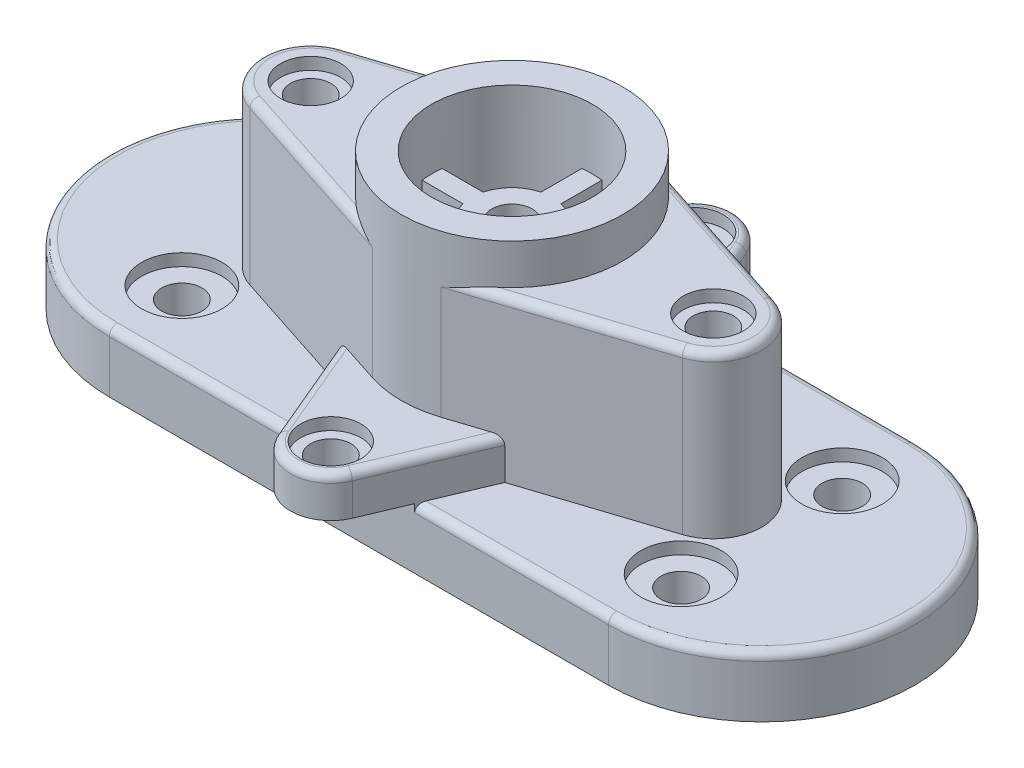
SolidWorks part; units mm, degrees
ref_plane "Front Plane" through (0, 0, 0) normal (0, 0, 1) x (1, 0, 0)
ref_plane "Top Plane" through (0, 0, 0) normal (0, 1, 0) x (1, 0, 0)
ref_plane "Right Plane" through (0, 0, 0) normal (1, 0, 0) x (0, 0, -1)
sketch "Sketch1" plane through (0, 0, 0) normal (0, 1, 0) x (1, 0, 0)
  line L0 (-62, 0) -> (62, 0) construction
  line L1 (-62, 38) -> (62, 38)
  line L2 (-62, -38) -> (62, -38)
  arc A0 (-62, 38) -> (-62, -38) centre (-62, 0) ccw
  arc A1 (62, -38) -> (62, 38) centre (62, 0) ccw
  point P2 (0, 0)
  dimension "D1" = 76
  dimension "D2" = 124
extrude "Boss-Extrude1" add sketch "Sketch1" along normal mid plane 15
sketch "Sketch2" plane through (0, 7.5, 0) normal (0, 1, 0) x (1, 0, 0)
  circle A0 centre (0, 0) radius 27.5
  dimension "D1" = 55
extrude "Boss-Extrude2" add sketch "Sketch2" along normal blind 50
hole_wizard "Hole1" positions "Sketch3" profile "Sketch4" legacy end condition through all
sketch "Sketch3" plane through (0, 7.5, 0) normal (0, 1, 0) x (1, 0, 0)
  point P0 (62, 20)
  dimension "D1" = 62
  dimension "D2" = 20
sketch "Sketch4" plane through (62, 7.5, -20) normal (1, 0, 0) x (0, 0, 1)
  line L0 (0, 0) -> (0, 18.0043)
  line L1 (0, 18.0043) -> (5, 15)
  line L2 (5, 15) -> (5, 3)
  line L3 (5, 3) -> (10, 3)
  line L4 (10, 0) -> (0, 0)
  line L5 (0, -11.3109) -> (0, 121.1557) construction
  line L6 (0, 18.0043) -> (-5, 15) construction
  line L7 (10, 3) -> (10, 0)
  dimension "Depth" = 15
  dimension "Drill Angle" = 118
  dimension "Diameter" = 10
  dimension "C-Bore Diameter" = 20
  dimension "C-Bore Depth" = 3
mirror "Mirror1" about plane through (0, 0, 0) normal (0, 0, 1) of "Hole1"
mirror "Mirror2" about plane through (0, 0, 0) normal (1, 0, 0) of "Hole1", "Mirror1"
hole_wizard "Hole2" positions "Sketch5" profile "Sketch6" legacy end condition through all
sketch "Sketch5" plane through (0, 57.5, 0) normal (0, 1, 0) x (1, 0, 0)
  point P0 (0, 0)
sketch "Sketch6" plane through (0, 57.5, 0) normal (1, 0, 0) x (0, 0, 1)
  line L0 (0, 0) -> (0, 68.0043)
  line L1 (0, 68.0043) -> (5, 65)
  line L2 (5, 65) -> (5, 15)
  line L3 (5, 15) -> (20, 15)
  line L4 (20, 0) -> (0, 0)
  line L5 (0, -11.3109) -> (0, 121.1557) construction
  line L6 (0, 68.0043) -> (-5, 65) construction
  line L7 (20, 15) -> (20, 0)
  dimension "Depth" = 65
  dimension "Drill Angle" = 118
  dimension "Diameter" = 10
  dimension "C-Bore Diameter" = 40
  dimension "C-Bore Depth" = 15
sketch "Sketch7" plane through (0, 7.5, 0) normal (0, 1, 0) x (1, 0, 0)
  line L0 (-53.72, 11.4088) -> (-8.525, 26.1453)
  line L1 (0, 0) -> (37.4038, 0) construction
  line L2 (0, 0) -> (0, 58.2008) construction
  line L3 (-53.72, -11.4088) -> (-8.525, -26.1453)
  line L4 (53.72, 11.4088) -> (8.525, 26.1453)
  line L5 (53.72, -11.4088) -> (8.525, -26.1453)
  circle A0 centre (0, 0) radius 27.5 construction
  arc A1 (-8.525, 26.1453) -> (-8.525, -26.1453) centre (0, 0) ccw
  arc A2 (-53.72, 11.4088) -> (-53.72, -11.4088) centre (-50, 0) ccw
  arc A3 (53.72, 11.4088) -> (53.72, -11.4088) centre (50, 0) cw
  arc A6 (8.525, -26.1453) -> (8.525, 26.1453) centre (0, 0) ccw
  dimension "D1" = 24
  dimension "D2" = 50
extrude "Boss-Extrude3" add sketch "Sketch7" along normal blind 40
hole_wizard "Hole3" positions "Sketch8" profile "Sketch9" legacy end condition through all
sketch "Sketch8" plane through (0, 47.5, 0) normal (0, 1, 0) x (1, 0, 0)
  point P0 (50, 0)
  point P3 (-50, 0)
sketch "Sketch9" plane through (50, 47.5, 0) normal (1, 0, 0) x (0, 0, 1)
  line L0 (0, 0) -> (0, 58.0043)
  line L1 (0, 58.0043) -> (5, 55)
  line L2 (5, 55) -> (5, 3)
  line L3 (5, 3) -> (7.5, 3)
  line L4 (7.5, 0) -> (0, 0)
  line L5 (0, -11.3109) -> (0, 121.1557) construction
  line L6 (0, 58.0043) -> (-5, 55) construction
  line L7 (7.5, 3) -> (7.5, 0)
  dimension "Depth" = 55
  dimension "Drill Angle" = 118
  dimension "Diameter" = 10
  dimension "C-Bore Diameter" = 15
  dimension "C-Bore Depth" = 3
sketch "Sketch10" plane through (0, 7.5, 0) normal (0, 1, 0) x (1, 0, 0)
  line L0 (-25.3353, 10.6944) -> (-9.2128, 48.8889)
  line L1 (0, 0) -> (47.9986, 0) construction
  line L2 (0, 0) -> (0, 24.0409) construction
  line L3 (25.3353, 10.6944) -> (9.2128, 48.8889)
  line L4 (-25.3353, -10.6944) -> (-9.2128, -48.8889)
  line L5 (25.3353, -10.6944) -> (9.2128, -48.8889)
  circle A0 centre (0, 0) radius 27.5 construction
  arc A1 (-25.3353, -10.6944) -> (25.3353, -10.6944) centre (0, 0) ccw
  arc A2 (9.2128, 48.8889) -> (-9.2128, 48.8889) centre (0, 45) ccw
  arc A3 (9.2128, -48.8889) -> (-9.2128, -48.8889) centre (0, -45) cw
  arc A4 (25.3353, 10.6944) -> (-25.3353, 10.6944) centre (0, 0) ccw
  dimension "D2" = 20
  dimension "D1" = 45
extrude "Boss-Extrude4" add sketch "Sketch10" along normal blind 10
hole_wizard "Hole4" positions "Sketch11" profile "Sketch12" legacy end condition through all
sketch "Sketch11" plane through (0, 17.5, 0) normal (0, 1, 0) x (1, 0, 0)
  point P0 (0, -45)
  point P3 (0, 45)
sketch "Sketch12" plane through (0, 17.5, 45) normal (1, 0, 0) x (0, 0, 1)
  line L0 (0, 0) -> (0, 28.0043)
  line L1 (0, 28.0043) -> (5, 25)
  line L2 (5, 25) -> (5, 3)
  line L3 (5, 3) -> (7.5, 3)
  line L4 (7.5, 0) -> (0, 0)
  line L5 (0, -11.3109) -> (0, 121.1557) construction
  line L6 (0, 28.0043) -> (-5, 25) construction
  line L7 (7.5, 3) -> (7.5, 0)
  dimension "Depth" = 25
  dimension "Drill Angle" = 118
  dimension "Diameter" = 10
  dimension "C-Bore Diameter" = 15
  dimension "C-Bore Depth" = 3
hole_wizard "Hole5" positions "Sketch14" profile "Sketch15" legacy
sketch "Sketch14" plane through (0, -7.5, 0) normal (0, -1, 0) x (-1, 0, 0)
  point P0 (0, 0)
sketch "Sketch15" plane through (0, -7.5, 0) normal (1, 0, 0) x (0, 0, -1)
  line L0 (0, 0) -> (0, 30)
  line L1 (0, 30) -> (22.5, 30)
  line L2 (22.5, 30) -> (22.5, 0)
  line L3 (22.5, 0) -> (0, 0)
  line L4 (0, 110) -> (0, -10) construction
  dimension "Diameter" = 45
  dimension "Depth" = 30
sketch "Sketch16" plane through (0, 42.5, 0) normal (0, 1, 0) x (1, 0, 0)
  line L0 (0, 10) -> (0, 33.946) construction
  line L1 (-2.5, 19.8431) -> (-2.5, 9.6825)
  line L3 (0, 0) -> (-30.0338, 0) construction
  line L8 (-19.8431, 2.5) -> (-9.6825, 2.5)
  circle A2 centre (0, 0) radius 20 construction
  arc A3 (-2.5, 19.8431) -> (-19.8431, 2.5) centre (0, 0) ccw
  arc A8 (-2.5, 9.6825) -> (-9.6825, 2.5) centre (0, 0) ccw
  point P25 (0, 0)
  dimension "D3" = 5
  dimension "D1" = 10
  dimension "D2" = 2.5
extrude "Cut-Extrude1" cut sketch "Sketch16" against normal through all
mirror "Mirror3" about plane through (0, 0, 0) normal (1, 0, 0) of "Cut-Extrude1"
mirror "Mirror4" about plane through (0, 0, 0) normal (0, 0, 1) of "Mirror3", "Cut-Extrude1"
fillet "Fillet1" radius 2 18 edges at (-14.8341, 17.5, -35.5721) (0, 17.5, -55) (-14.8341, 17.5, 35.5721) (14.8341, 17.5, 35.5721) (-31.1225, 47.5, 18.777) (-62, 47.5, 0) (31.1225, 47.5, 18.777) (31.1225, 47.5, -18.777) (-37.9046, 7.5, -38) (-37.9046, 7.5, 38) (37.9046, 7.5, 38) (37.9046, 7.5, -38) (14.8341, 17.5, -35.5721) (0, 17.5, 55) (-31.1225, 47.5, -18.777) (62, 47.5, 0) (-100, 7.5, 0) (100, 7.5, 0)
